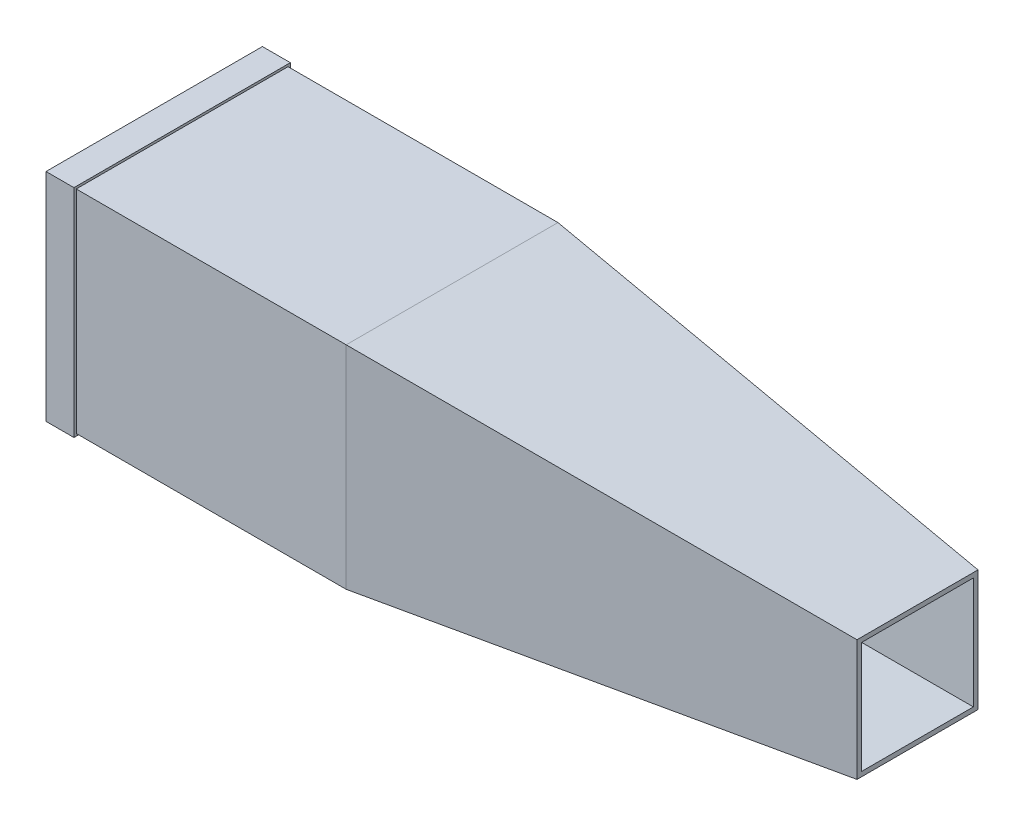
SolidWorks part; units mm, degrees
ref_plane "Front Plane" through (0, 0, 0) normal (0, 0, 1) x (1, 0, 0)
ref_plane "Top Plane" through (0, 0, 0) normal (0, 1, 0) x (1, 0, 0)
ref_plane "Right Plane" through (0, 0, 0) normal (1, 0, 0) x (0, 0, -1)
sketch "Sketch1" plane through (0, 0, 0) normal (1, 0, 0) x (0, 0, -1)
  line L1 (-116.25, 116.25) -> (116.25, 116.25)
  line L2 (-116.25, 116.25) -> (-116.25, -116.25)
  line L3 (-116.25, -116.25) -> (116.25, -116.25)
  line L4 (116.25, 116.25) -> (116.25, -116.25)
  line L5 (-116.25, 116.25) -> (116.25, -116.25) construction
  line L6 (-116.25, -116.25) -> (116.25, 116.25) construction
  line L7 (-111.25, 111.25) -> (111.25, 111.25)
  line L8 (-111.25, 111.25) -> (-111.25, -111.25)
  line L9 (-111.25, -111.25) -> (111.25, -111.25)
  line L10 (111.25, 111.25) -> (111.25, -111.25)
  line L11 (-111.25, 111.25) -> (111.25, -111.25) construction
  line L12 (-111.25, -111.25) -> (111.25, 111.25) construction
  point P0 (0, 0)
  point P6 (0, 0)
  dimension "D1" = 232.5
  dimension "D2" = 232.5
  dimension "D3" = 5
  dimension "D4" = 5
extrude "Boss-Extrude1" add sketch "Sketch1" along normal blind 30
ref_plane "Plane1" through (20, 0, 0) normal (1, 0, 0) x (0, 0, -1)
sketch "Sketch3" plane through (20, 0, 0) normal (1, 0, 0) x (0, 0, -1)
  line L0 (116.25, 116.25) -> (-116.25, 116.25) construction
  line L1 (-113.75, -113.75) -> (113.75, -113.75)
  line L2 (-113.75, -113.75) -> (-113.75, 113.75)
  line L3 (-113.75, 113.75) -> (113.75, 113.75)
  line L4 (113.75, -113.75) -> (113.75, 113.75)
  line L5 (-113.75, -113.75) -> (113.75, 113.75) construction
  line L6 (-113.75, 113.75) -> (113.75, -113.75) construction
  line L7 (-116.25, 116.25) -> (-116.25, -116.25) construction
  line L9 (-108.75, 108.75) -> (108.75, 108.75)
  line L10 (-108.75, 108.75) -> (-108.75, -108.75)
  line L11 (-108.75, -108.75) -> (108.75, -108.75)
  line L12 (108.75, 108.75) -> (108.75, -108.75)
  line L13 (-108.75, 108.75) -> (108.75, -108.75) construction
  line L14 (-108.75, -108.75) -> (108.75, 108.75) construction
  point P0 (0, 0)
  point P10 (0, 0)
  dimension "D1" = 2.5
  dimension "D2" = 2.5
  dimension "D3" = 5
  dimension "D4" = 5
extrude "Boss-Extrude2" add sketch "Sketch3" along normal blind 300
ref_plane "Plane2" through (820, 0, 0) normal (1, 0, 0) x (0, 0, -1)
sketch "Sketch4" plane through (820, 0, 0) normal (1, 0, 0) x (0, 0, -1)
  line L1 (-60, 60) -> (60, 60)
  line L2 (-60, 60) -> (-60, -60)
  line L3 (-60, -60) -> (60, -60)
  line L4 (60, 60) -> (60, -60)
  line L5 (-60, 60) -> (60, -60) construction
  line L6 (-60, -60) -> (60, 60) construction
  line L7 (-65, 65) -> (65, 65)
  line L8 (-65, 65) -> (-65, -65)
  line L9 (-65, -65) -> (65, -65)
  line L10 (65, 65) -> (65, -65)
  line L11 (-65, 65) -> (65, -65) construction
  line L12 (-65, -65) -> (65, 65) construction
  point P0 (0, 0)
  point P6 (0, 0)
  dimension "D1" = 120
  dimension "D2" = 120
  dimension "D3" = 5
  dimension "D4" = 5
sketch "Sketch5" plane through (320, 0, 0) normal (1, 0, 0) x (0, 0, -1)
  line L1 (-108.75, 108.75) -> (108.75, 108.75)
  line L2 (-108.75, 108.75) -> (-108.75, -108.75)
  line L3 (-108.75, -108.75) -> (108.75, -108.75)
  line L4 (108.75, 108.75) -> (108.75, -108.75)
  line L5 (-108.75, 108.75) -> (108.75, -108.75) construction
  line L6 (-108.75, -108.75) -> (108.75, 108.75) construction
  line L7 (-113.75, 113.75) -> (113.75, 113.75)
  line L8 (-113.75, 113.75) -> (-113.75, -113.75)
  line L9 (-113.75, -113.75) -> (113.75, -113.75)
  line L10 (113.75, 113.75) -> (113.75, -113.75)
  line L11 (-113.75, 113.75) -> (113.75, -113.75) construction
  line L12 (-113.75, -113.75) -> (113.75, 113.75) construction
  point P0 (0, 0)
  point P7 (0, 0)
loft "Loft2" add section "Sketch5" section "Sketch4" connector at (320, 113.75, 113.75) connector at (820, 65, 65)
loft "Cut-Loft2" cut section "Sketch5<5>" section "Sketch4<7>" connector at (320, 108.75, 108.75) connector at (820, 60, 60)
sketch "Sketch5<5>" plane through (320, 0, 0) normal (1, 0, 0) x (0, 0, -1) same geometry as "Sketch5"
sketch "Sketch4<7>" plane through (820, 0, 0) normal (1, 0, 0) x (0, 0, -1) same geometry as "Sketch4"
ref_plane "Plane3" through (165, 0, 0) normal (1, 0, 0) x (0, 0, -1)
sketch "Sketch8" plane through (165, 0, 0) normal (1, 0, 0) x (0, 0, -1)
  line L0 (108.75, 108.75) -> (-108.75, 108.75) construction
  line L1 (111.25, 111.25) -> (-111.25, 111.25)
  line L2 (111.25, 111.25) -> (111.25, -111.25)
  line L3 (111.25, -111.25) -> (-111.25, -111.25)
  line L4 (-111.25, 111.25) -> (-111.25, -111.25)
  line L5 (111.25, 111.25) -> (-111.25, -111.25) construction
  line L6 (111.25, -111.25) -> (-111.25, 111.25) construction
  line L7 (-111.25, 111.25) -> (111.25, 111.25) construction
  line L8 (111.25, 111.25) -> (111.25, -111.25) construction
  line L9 (108.75, 108.75) -> (-108.75, 108.75)
  line L10 (108.75, 108.75) -> (108.75, -108.75)
  line L11 (108.75, -108.75) -> (-108.75, -108.75)
  line L12 (-108.75, 108.75) -> (-108.75, -108.75)
  line L13 (108.75, 108.75) -> (-108.75, -108.75) construction
  line L14 (108.75, -108.75) -> (-108.75, 108.75) construction
  line L15 (108.75, -108.75) -> (108.75, 108.75) construction
  point P0 (0, 0)
  point P10 (0, 0)
  dimension "D1" = 0
  dimension "D2" = 0
  dimension "D3" = 0
  dimension "D4" = 0
extrude "Cut-Extrude1" cut sketch "Sketch8" against normal blind 2 and the other way blind 2
